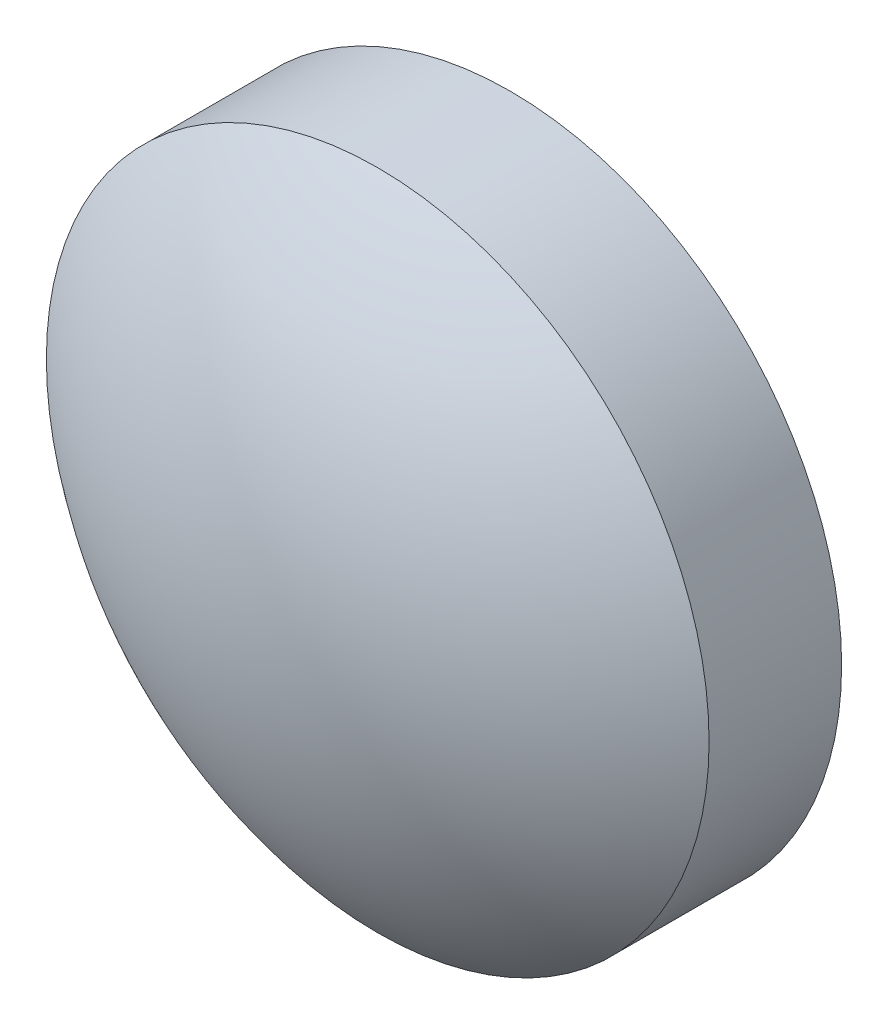
SolidWorks part; units mm, degrees
ref_plane "Front Plane" through (0, 0, 0) normal (0, 0, 1) x (1, 0, 0)
ref_plane "Top Plane" through (0, 0, 0) normal (0, 1, 0) x (1, 0, 0)
ref_plane "Right Plane" through (0, 0, 0) normal (1, 0, 0) x (0, 0, -1)
sketch "Sketch1" plane through (0, 0, 0) normal (0, 0, 1) x (1, 0, 0)
  circle A0 centre (0, 0) radius 2.5
  dimension "D1" = 5
extrude "Boss-Extrude1" add sketch "Sketch1" along normal blind 1
sketch "Sketch4" plane through (0, 0, 0) normal (0, 1, 0) x (1, 0, 0)
  line L2 (-2.5, -1) -> (2.5, -1)
  line L4 (0, -1) -> (0, -1.8889) construction
  arc A0 (-2.5, -1) -> (2.5, -1) centre (0, 2.0711) ccw
revolve "Revolve8" add sketch "Sketch4" angle 360 about L4 region at (0.9533, 0, 1.3592)
